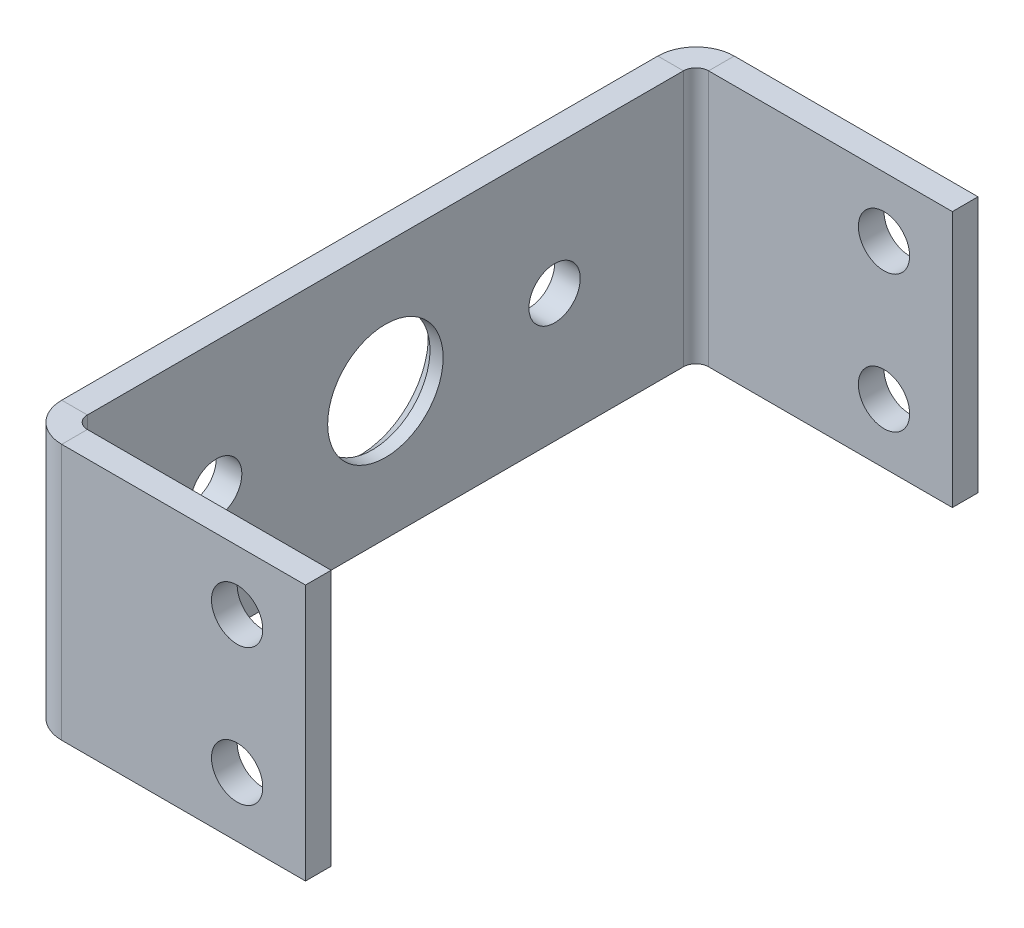
SolidWorks part; units mm, degrees
note: The reader was unsure of these and kept them because the rebuilt part matched: bend radius of "Pliegue base3", "Pliegue base4".
material "ABS"
ref_plane "Alzado" through (0, 0, 0) normal (0, 0, 1) x (1, 0, 0)
ref_plane "Planta" through (0, 0, 0) normal (0, 1, 0) x (1, 0, 0)
ref_plane "Vista lateral" through (0, 0, 0) normal (1, 0, 0) x (0, 0, -1)
sketch "Croquis1" plane through (122.0524, 0, 0) normal (0, 1, 0) x (1, 0, 0)
  line L0 (-107.0524, 18.175) -> (-122.0524, 18.175)
  line L2 (-122.0524, 18.175) -> (-122.0524, -18.175)
  line L3 (-122.0524, -18.175) -> (-107.0524, -18.175)
  dimension "D1" = 15
  dimension "D2" = 36.35
base flange "Brida base2" sketch "Croquis1" end condition mid plane depth 15 reverse direction no thickness 1.5 reverse thickness direction no bend radius 0.7366
bend "Pliegue base3" bend radius 0.7366 bend angle 90 parameters "D5"=1
bend "Pliegue base4" bend radius 0.7366 bend angle 90 parameters "D5"=2
sketch "Croquis10" plane through (0, 0, -19.675) normal (0, 0, -1) x (-1, 0, 0)
  line L0 (-11, 4) -> (-11, -4) construction
  line L1 (-15, 7.5) -> (-15, -7.5) construction
  circle A0 centre (-11, 4) radius 1.5
  circle A1 centre (-11, -4) radius 1.5
  point P10 (-11, 0)
  dimension "D1" = 3
  dimension "D2" = 8
  dimension "D3" = 4
extrude "Cortar-Extruir1" cut sketch "Croquis10" against normal through all normal cut yes
sketch "Croquis13" plane through (0, 0, 0) normal (1, 0, 0) x (0, 0, 1)
  line L0 (-17.4384, 0) -> (-9.9, 0) construction
  line L3 (-17.4384, -7.5) -> (-17.4384, 7.5) construction
  line L4 (-9.9, 0) -> (9.9, 0) construction
  line L5 (9.9, 0) -> (17.4384, 0) construction
  line L6 (17.4384, -7.5) -> (17.4384, 7.5) construction
  circle A0 centre (-9.9, 0) radius 1.5
  circle A1 centre (9.9, 0) radius 1.5
  dimension "D1" = 19.8
  dimension "D2" = 3
extrude "Cortar-Extruir2" cut sketch "Croquis13" against normal up to next normal cut yes
sketch "Croquis14" plane through (-1.5, 0, 0) normal (-1, 0, 0) x (0, 0, 1)
  circle A0 centre (0, 0) radius 3.56
  dimension "D1" = 7.12
sketch "Croquis18" plane through (-1.5, 0, 0) normal (-1, 0, 0) x (0, 0, 1)
  point P0 (0, 0)
sketch "Croquis23" plane through (-1.5, 0, 0) normal (-1, 0, 0) x (0, 0, 1)
  point P0 (0, 0)
hole_wizard "Taladro de margen para 1/41" positions "Croquis23" profile "Croquis20" hole size "1/4" standard "Ansi Inch"
sketch "Croquis20" plane through (-1.5, 0, 0) normal (0, 1, 0) x (0, 0, 1)
  line L0 (0, 0) -> (0, 5.6798)
  line L1 (0, 5.6798) -> (3.3782, 3.65)
  line L2 (3.3782, 3.65) -> (3.3782, 0.7305)
  line L3 (3.3782, 0.7305) -> (4.0132, 0)
  line L5 (4.0132, 0) -> (0, 0)
  line L6 (-3.3782, 0.7305) -> (-4.0132, 0) construction
  line L10 (0, 5.6798) -> (-3.3782, 3.65) construction
  line L11 (0, -6.35) -> (0, 107.95) construction
  dimension "Diámetro de taladro" = 6.7564
  dimension "Profundidad de taladro" = 3.65
  dimension "Diámetro de avellanado cercano" = 8.0264
  dimension "Ángulo de avellanado cercano" = 82
  dimension "Ángulo de perforador" = 118
sketch "Líneas de pliegue3" plane through (0, 0, 0) normal (0, 1, 0) x (1, 0, 0)
sketch "Cuadro delimitador3" plane through (0, 0, 0) normal (0, 1, 0) x (1, 0, 0)
sheet metal parameters "Chapa metálica(2)" thickness 1.5 parameters "D1"=0.7366
flat pattern "Chapa desplegada(2)" [suppressed]
sketch "Líneas de pliegue4" plane through (0, 0, 0) normal (0, 1, 0) x (1, 0, 0)
sketch "Cuadro delimitador4" [suppressed] plane through (0, 0, 0) normal (0, 1, 0) x (1, 0, 0)
bend of the flat pattern "Aplanar-<Pliegue base3>1"
bend of the flat pattern "Aplanar-<Pliegue base4>1"
sheet metal parameters "Chapa metálica(3)" thickness 1.5 parameters "D1"=0.7366
flat pattern "Chapa desplegada(2)" [suppressed]
sketch "Líneas de pliegue5" plane through (0, 0, 0) normal (0, 1, 0) x (1, 0, 0)
sketch "Cuadro delimitador5" [suppressed] plane through (0, 0, 0) normal (0, 1, 0) x (1, 0, 0)
bend of the flat pattern "Aplanar-<Pliegue base3>2"
bend of the flat pattern "Aplanar-<Pliegue base4>2"
sheet metal parameters "Chapa metálica(4)" thickness 1.5 parameters "D1"=0.7366
flat pattern "Chapa desplegada(2)" [suppressed]
sketch "Líneas de pliegue6" plane through (0, 0, 0) normal (0, 1, 0) x (1, 0, 0)
sketch "Cuadro delimitador6" [suppressed] plane through (0, 0, 0) normal (0, 1, 0) x (1, 0, 0)
bend of the flat pattern "Aplanar-<Pliegue base3>3"
bend of the flat pattern "Aplanar-<Pliegue base4>3"
sheet metal parameters "Chapa metálica(7)" thickness 1.5 parameters "D1"=0.7366
flat pattern "Chapa desplegada(2)" [suppressed]
sketch "Líneas de pliegue6" plane through (0, 0, 0) normal (0, 1, 0) x (1, 0, 0)
sketch "Cuadro delimitador6" [suppressed] plane through (0, 0, 0) normal (0, 1, 0) x (1, 0, 0)
bend of the flat pattern "Aplanar-<Pliegue base3>3"
bend of the flat pattern "Aplanar-<Pliegue base4>3"
